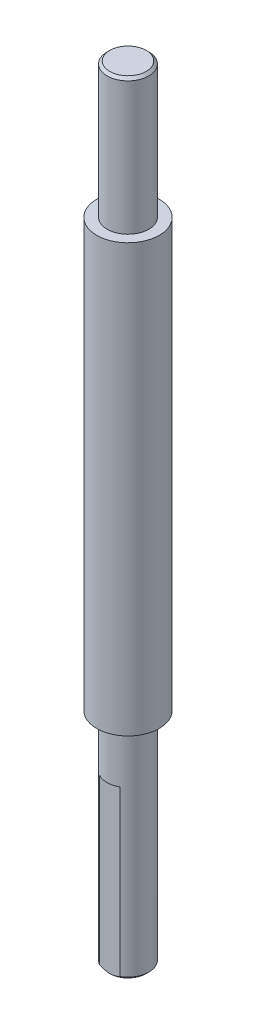
SolidWorks part; units mm, degrees
material "E24"
ref_plane "Plan de face" through (0, 0, 0) normal (0, 0, 1) x (1, 0, 0)
ref_plane "Plan de dessus" through (0, 0, 0) normal (0, 1, 0) x (1, 0, 0)
ref_plane "Plan de droite" through (0, 0, 0) normal (1, 0, 0) x (0, 0, -1)
sketch "Sketch1" plane through (0, 0, 0) normal (0, 1, 0) x (1, 0, 0)
  circle A0 centre (0, 0) radius 6
  dimension "D1" = 12
extrude "Boss-Extrude1" add sketch "Sketch1" along normal blind 150
sketch "Sketch2" plane through (0, 150, 0) normal (0, 1, 0) x (1, 0, 0)
  circle A0 centre (0, 0) radius 4
  dimension "D1" = 8
extrude "Cut-Extrude1" cut sketch "Sketch2" against normal blind 26 flip side to cut
sketch "Sketch3" plane through (0, 0, 0) normal (0, -1, 0) x (1, 0, 0)
  circle A0 centre (0, 0) radius 4
  dimension "D1" = 8
extrude "Cut-Extrude2" cut sketch "Sketch3" against normal offset from surface (42 mm away) 82 flip side to cut up to face at (0, 124, 4)
sketch "Sketch4" plane through (0, 0, 0) normal (1, 0, 0) x (0, 0, -1)
  line L1 (-4, 0) -> (-3.5, 0)
  line L2 (-4, 0) -> (-4, 32)
  line L3 (-4, 32) -> (-3.5, 32)
  line L4 (-3.5, 0) -> (-3.5, 32)
  dimension "D1" = 0.5
  dimension "D2" = 32
extrude "Cut-Extrude3" cut sketch "Sketch4" against normal mid plane 10
chamfer "Chamfer1" distance 0.5 angle 45 2 edges at (0, 0, -4) (0, 150, 4)
